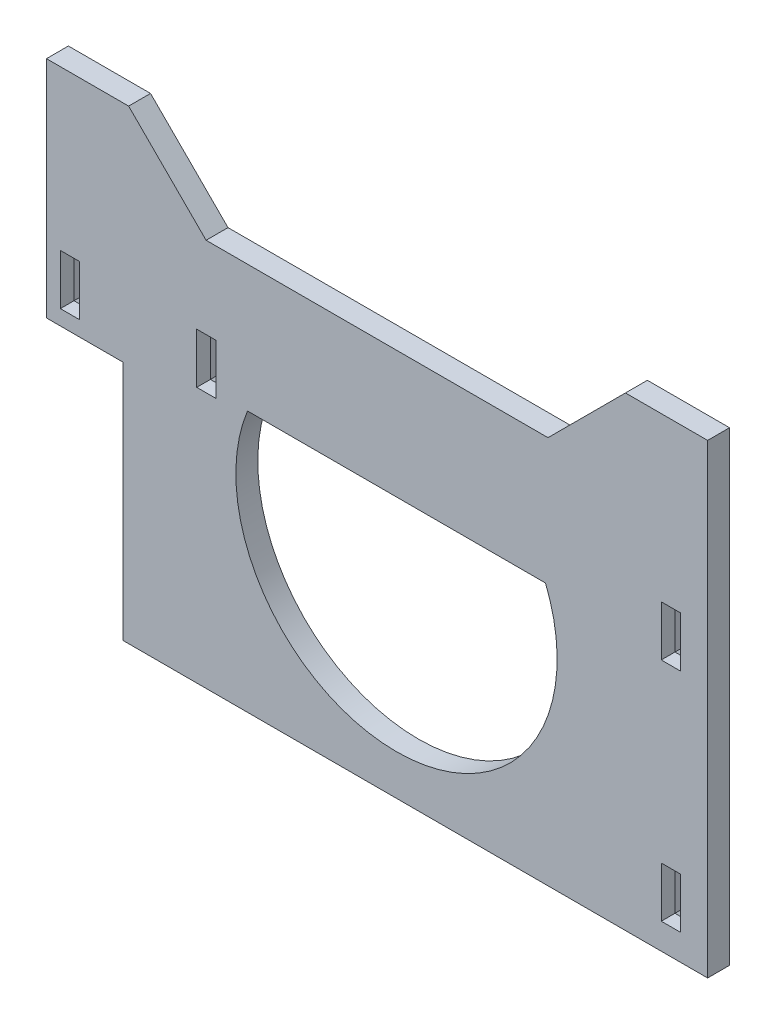
SolidWorks part; units mm, degrees
ref_plane "Front Plane" through (0, 0, 0) normal (0, 0, 1) x (1, 0, 0)
ref_plane "Top Plane" through (0, 0, 0) normal (0, 1, 0) x (1, 0, 0)
ref_plane "Right Plane" through (0, 0, 0) normal (1, 0, 0) x (0, 0, -1)
sketch "Sketch1" plane through (0, 0, 0) normal (0, 0, 1) x (1, 0, 0)
  line L0 (-31.5106, 17.6478) -> (22.8986, 17.6478)
  line L6 (-40.7725, 25.95) -> (-37.2425, 25.95)
  line L9 (-40.7725, 25.95) -> (-40.7725, 16.75)
  line L12 (-40.7725, 16.75) -> (-37.2425, 16.75)
  line L15 (-37.2425, 25.95) -> (-37.2425, 16.75)
  line L51 (52.4925, 30) -> (52.4925, -30)
  line L54 (44.0275, 25.25) -> (47.5575, 25.25)
  line L55 (44.0275, 25.25) -> (44.0275, 16.05)
  line L56 (44.0275, 16.05) -> (47.5575, 16.05)
  line L57 (47.5575, 25.25) -> (47.5575, 16.05)
  line L58 (47.565, -16.05) -> (44.035, -16.05)
  line L59 (47.565, -16.05) -> (47.565, -25.25)
  line L60 (47.565, -25.25) -> (44.035, -25.25)
  line L61 (44.035, -16.05) -> (44.035, -25.25)
  line L65 (-65.6725, 25.95) -> (-62.1425, 25.95)
  line L66 (-65.6725, 25.95) -> (-65.6725, 16.75)
  line L67 (-65.6725, 16.75) -> (-62.1425, 16.75)
  line L68 (-62.1425, 25.95) -> (-62.1425, 16.75)
  line L76 (52.4925, 30) -> (-68.2075, 30)
  line L81 (-39.0075, 25.95) -> (-39.0075, 16.75) construction
  line L82 (-37.2425, 21.35) -> (-40.7725, 21.35) construction
  line L83 (-63.9075, 25.95) -> (-63.9075, 16.75) construction
  line L84 (-62.1425, 21.35) -> (-65.6725, 21.35) construction
  line L85 (47.5575, 20.65) -> (44.0275, 20.65) construction
  line L86 (45.7925, 25.25) -> (45.7925, 16.05) construction
  line L87 (45.8, -16.05) -> (45.8, -25.25) construction
  line L88 (47.565, -20.65) -> (44.035, -20.65) construction
  line L89 (-54.2075, -30) -> (-54.2075, 14)
  line L90 (-54.2075, 14) -> (-68.2075, 14)
  line L91 (-68.2075, 14) -> (-68.2075, 30)
  line L92 (-54.2075, -30) -> (52.4925, -30)
  arc A12 (-31.5106, 17.6478) -> (22.8986, 17.6478) centre (-4.306, 6.6977) ccw
  point P0 (-0.0075, 0)
  point P14 (52.4925, 0)
  point P25 (-7.8575, 30)
  dimension "D3" = 3.53
  dimension "D4" = 9.2
  dimension "D6" = 60
  dimension "D5" = 24.9
  dimension "D7" = 53.65
  dimension "D2" = 31.15
  dimension "D10" = 20.65
  dimension "D11" = 20.65
  dimension "D8" = 120.7
  dimension "D9" = 14
  dimension "D12" = 44
extrude "Boss-Extrude1" add sketch "Sketch1" along normal blind 4
sketch "Sketch2" plane through (0, 0, 0) normal (0, 0, 1) x (1, 0, 0)
  line L0 (-68.2075, 30) -> (52.4925, 30)
  line L4 (23.3504, 40.8579) -> (-39.0654, 40.8579)
  line L5 (-39.0654, 40.8579) -> (-53.2075, 55)
  line L6 (-53.2075, 55) -> (-68.2075, 55)
  line L7 (-68.2075, 55) -> (-68.2075, 30)
  line L8 (23.3504, 40.8579) -> (37.4925, 55)
  line L9 (37.4925, 55) -> (52.4925, 55)
  line L10 (52.4925, 55) -> (52.4925, 30)
  line L12 (-68.2075, 30) -> (-68.2075, 14) construction
  dimension "D1" = 25
  dimension "D2" = 20
  dimension "D3" = 15
  dimension "D4" = 135
extrude "Boss-Extrude2" add sketch "Sketch2" along normal blind 4
sketch "Sketch3" plane through (0, 0, 0) normal (0, 0, -1) x (-1, 0, 0)
  line L0 (-45.7925, 25.25) -> (-45.7925, 16.05) construction
  line L1 (-47.5575, 25.25) -> (-44.0275, 25.25) construction
  line L2 (-44.0275, 16.05) -> (-47.5575, 16.05) construction
  line L3 (-47.5575, 20.65) -> (-44.0275, 20.65) construction
  line L4 (-47.5575, 16.05) -> (-47.5575, 25.25) construction
  line L5 (-44.0275, 25.25) -> (-44.0275, 16.05) construction
  line L6 (-45.8, -16.05) -> (-45.8, -25.25) construction
  line L7 (-47.565, -16.05) -> (-44.035, -16.05) construction
  line L8 (-44.035, -25.25) -> (-47.565, -25.25) construction
  line L9 (-47.565, -20.65) -> (-44.035, -20.65) construction
  line L10 (-47.565, -25.25) -> (-47.565, -16.05) construction
  line L11 (-44.035, -16.05) -> (-44.035, -25.25) construction
  line L12 (39.0075, 25.95) -> (39.0075, 16.75) construction
  line L13 (37.2425, 25.95) -> (40.7725, 25.95) construction
  line L14 (40.7725, 16.75) -> (37.2425, 16.75) construction
  line L15 (37.2425, 21.35) -> (40.7725, 21.35) construction
  line L16 (37.2425, 16.75) -> (37.2425, 25.95) construction
  line L17 (40.7725, 25.95) -> (40.7725, 16.75) construction
  line L18 (63.9075, 25.95) -> (63.9075, 16.75) construction
  line L19 (62.1425, 25.95) -> (65.6725, 25.95) construction
  line L20 (65.6725, 16.75) -> (62.1425, 16.75) construction
  line L21 (62.1425, 21.35) -> (65.6725, 21.35) construction
  line L22 (62.1425, 16.75) -> (62.1425, 25.95) construction
  line L23 (65.6725, 25.95) -> (65.6725, 16.75) construction
chamfer "Chamfer1" distance 1.5 distance2 0.5 16 edges at (45.8, -25.25, 0) (44.035, -20.65, 0) (45.8, -16.05, 0) (47.565, -20.65, 0) (-63.9075, 25.95, 0) (-62.1425, 21.35, 0) (-63.9075, 16.75, 0) (-65.6725, 21.35, 0) (-39.0075, 25.95, 0) (-37.2425, 21.35, 0) (-39.0075, 16.75, 0) (-40.7725, 21.35, 0) (45.7925, 25.25, 0) (47.5575, 20.65, 0) (45.7925, 16.05, 0) (44.0275, 20.65, 0) first distance on face at (45.8, -25.25, 2) first distance on face at (44.035, -20.65, 2) first distance on face at (45.8, -16.05, 2) first distance on face at (47.565, -20.65, 2) first distance on face at (-63.9075, 25.95, 2) first distance on face at (-62.1425, 21.35, 2) first distance on face at (-63.9075, 16.75, 2) first distance on face at (-65.6725, 21.35, 2) first distance on face at (-39.0075, 25.95, 2) first distance on face at (-37.2425, 21.35, 2) first distance on face at (-39.0075, 16.75, 2) first distance on face at (-40.7725, 21.35, 2) first distance on face at (45.7925, 25.25, 2) first distance on face at (47.5575, 20.65, 2) first distance on face at (45.7925, 16.05, 2) first distance on face at (44.0275, 20.65, 2)
equation "\"pin_hole_width\"=3.53"
equation "\"D3@Sketch1\"=\"pin_hole_width\""
equation "\"pin_hole_height\"=9.2"
equation "\"D4@Sketch1\"=\"pin_hole_height\""
equation "\"distancer\"=24.9"
equation "\"D5@Sketch1\"=\"distancer\""
